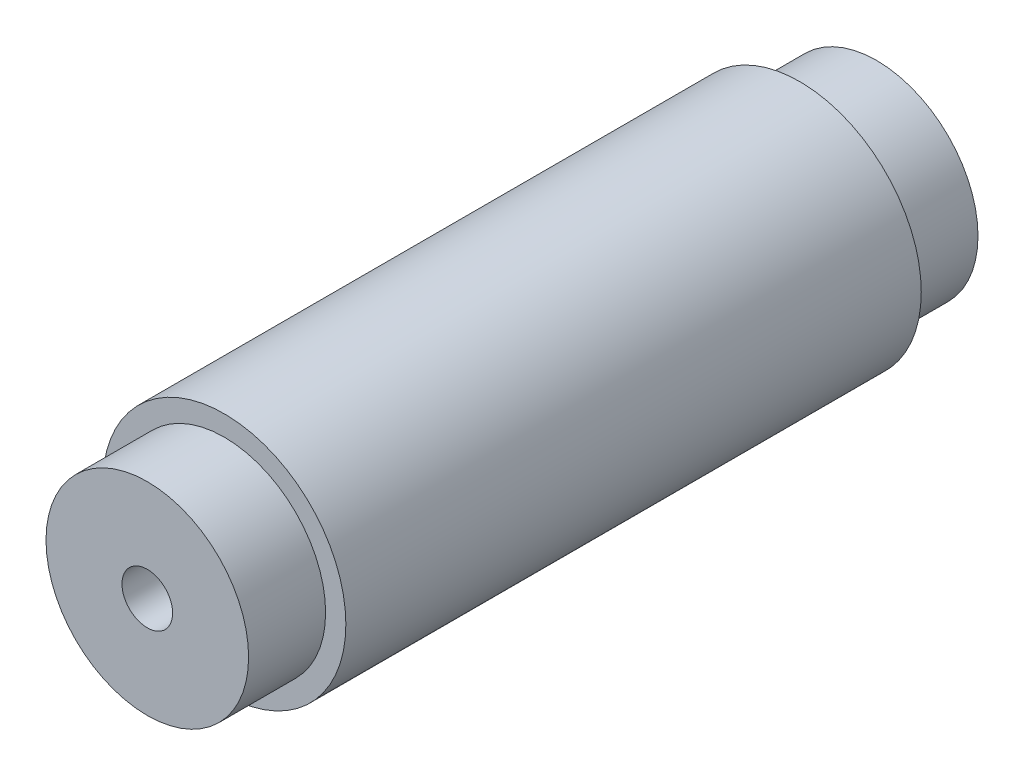
SolidWorks part; units mm, degrees
ref_plane "正面" through (0, 0, 0) normal (0, 0, 1) x (1, 0, 0)
ref_plane "平面" through (0, 0, 0) normal (0, 1, 0) x (1, 0, 0)
ref_plane "右側面" through (0, 0, 0) normal (1, 0, 0) x (0, 0, -1)
sketch "ｽｹｯﾁ1" plane through (0, 0, 0) normal (0, 0, 1) x (1, 0, 0)
  circle A0 centre (0, 0) radius 6
  dimension "D1" = 12
extrude "ﾎﾞｽ - 押し出し1" add sketch "ｽｹｯﾁ1" along normal blind 36
sketch "ｽｹｯﾁ2" plane through (0, 0, 36) normal (0, 0, 1) x (1, 0, 0)
  circle A0 centre (0, 0) radius 6
  circle A1 centre (0, 0) radius 5
  circle A2 centre (0, 0) radius 6 construction
  dimension "D1" = 10
extrude "ｶｯﾄ - 押し出し1" cut sketch "ｽｹｯﾁ2" against normal blind 3.8
ref_plane "平面1" through (0, 0, 18) normal (0, 0, 1) x (1, 0, 0)
sketch "ｽｹｯﾁ3" plane through (0, 0, 36) normal (0, 0, 1) x (1, 0, 0)
  circle A0 centre (0, 0) radius 1.25
  dimension "D1" = 2.5
extrude "ｶｯﾄ - 押し出し2" cut sketch "ｽｹｯﾁ3" against normal blind 10
ref_plane "平面2" through (0, 0, 18) normal (0, 0, 1) x (1, 0, 0)
mirror "ﾐﾗｰ1" about plane through (0, 0, 18) normal (0, 0, 1) of "ｶｯﾄ - 押し出し1"
